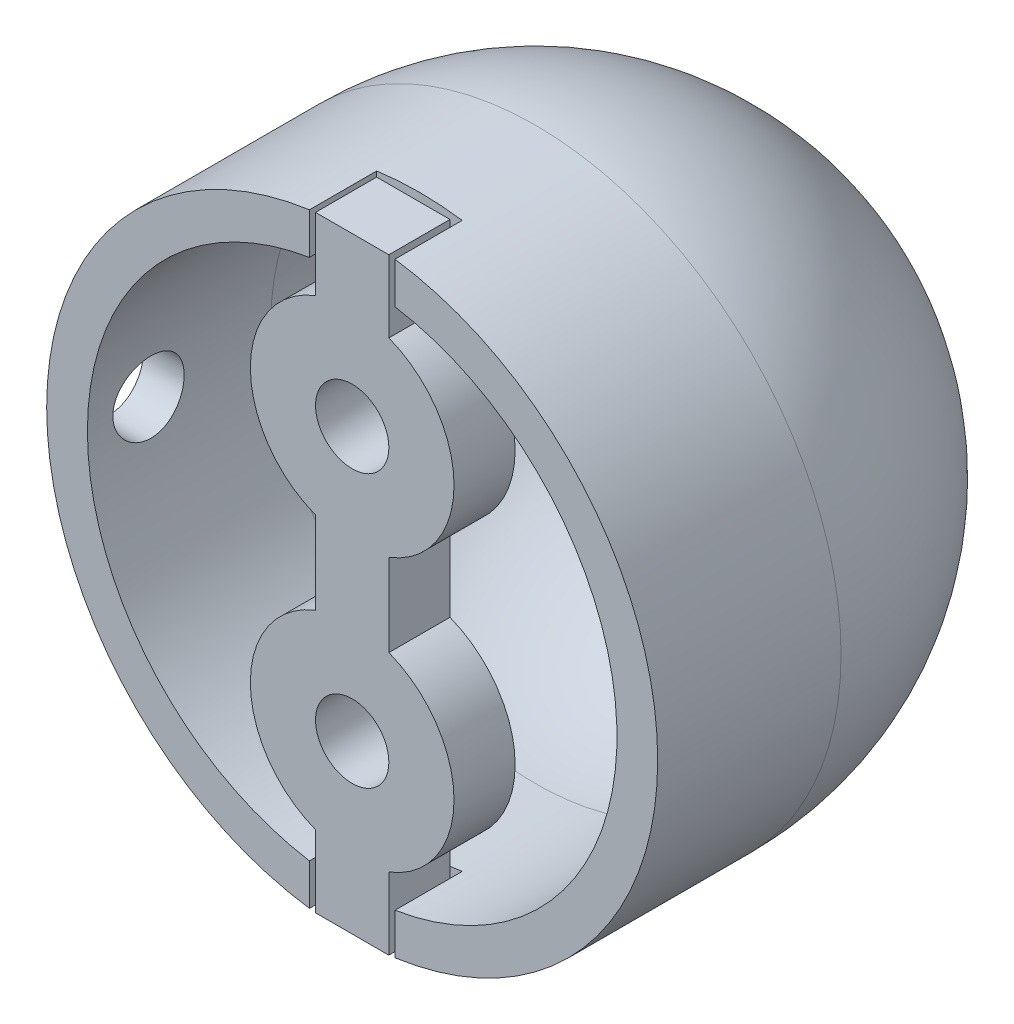
SolidWorks part; units mm, degrees
ref_plane "Front Plane" through (0, 0, 0) normal (0, 0, 1) x (1, 0, 0)
ref_plane "Top Plane" through (0, 0, 0) normal (0, 1, 0) x (1, 0, 0)
ref_plane "Right Plane" through (0, 0, 0) normal (1, 0, 0) x (0, 0, -1)
sketch "Sketch2" plane through (0, 0, 0) normal (0, 1, 0) x (1, 0, 0)
  line L19 (0, 0) -> (0, -9)
  line L20 (0, -9) -> (2, -9)
  line L30 (28, -8.3222) -> (28, -9)
  line L31 (28, -9) -> (30, -9)
  line L32 (2, -7) -> (28, -7) construction
  line L33 (0, -9) -> (30, -9) construction
  line L34 (2, 0) -> (2, -7) construction
  line L35 (28, 0) -> (28, -7) construction
  line L36 (2, 0) -> (2, -9)
  line L37 (28, 0) -> (28, -9)
  line L38 (15, 26.392) -> (15, -5.1789) construction
  line L39 (31.2383, -7.5) -> (-1.9776, -7.5) construction
  line L40 (30, 0) -> (30, -9) construction
  line L41 (30, 0) -> (30, -9)
  line L43 (15, 15) -> (15, 13)
  line L44 (0, -6) -> (2, -6)
  line L46 (34.9987, -7.7947) -> (34.8093, -7.7947)
  line L47 (34.9987, -7.7947) -> (34.9987, -6.81)
  line L48 (34.9987, -6.81) -> (34.8093, -6.81)
  line L49 (34.8093, -7.7947) -> (34.8093, -6.81)
  arc A2 (0, 0) -> (30, 0) centre (15, 0) cw
  arc A3 (2, 0) -> (28, 0) centre (15, 0) cw
  point P21 (15, 13)
  dimension "D1" = 2
  dimension "D2" = 22
  dimension "D3" = 3
  dimension "D4" = 1.5
  dimension "D5" = 26
revolve "Revolve3" add sketch "Sketch2" angle 360 about L38 region at (4.5759, 0, -10.4241) region at (1, 0, 7.5) other way angle 360
sketch "Sketch4" plane through (0, 0, 0) normal (1, 0, 0) x (0, 0, -1)
  line L0 (-9, 0) -> (-9, 13.7954) construction
  line L1 (-9, 0) -> (-4.2824, 0) construction
  line L2 (13.2, 0) -> (-13.2, 0) construction
  line L3 (-6, 0) -> (-6, 5.4849) construction
  line L4 (-9, 15) -> (-9, -15) construction
  circle A0 centre (-6, 0) radius 1.75
  dimension "D1" = 3
  dimension "D2" = 0
extrude "Cut-Extrude1" cut sketch "Sketch4" along normal blind 10 contours A0
ref_plane "Plane1" through (0, 0, 9) normal (0, 0, 1) x (1, 0, 0)
sketch "Sketch5" plane through (0, 0, 9) normal (0, 0, 1) x (1, 0, 0)
  line L0 (30, 0) -> (0, 0) construction
  line L1 (15, -13) -> (15, 15) construction
  line L2 (15, -4.8901) -> (30, 0) construction
  line L3 (30, 0) -> (15, 4.8901) construction
  line L4 (16.8, -6.6901) -> (16.8, 6.6901)
  line L5 (16.8, 6.6901) -> (16.8, 14.8916)
  line L6 (16.8, 14.8916) -> (13.2, 14.8916)
  line L7 (13.2, 14.8916) -> (13.2, 6.6901)
  line L8 (13.2, 6.6901) -> (13.2, -6.6901)
  line L9 (13.2, -6.6901) -> (13.2, -14.8916)
  line L10 (13.2, -14.8916) -> (16.8, -14.8916)
  line L11 (16.8, -14.8916) -> (16.8, -6.6901)
  line L13 (17.1, -15) -> (12.9, -15)
  line L14 (17.1, -15) -> (17.1, 15)
  line L15 (17.1, 15) -> (12.9, 15)
  line L16 (12.9, -15) -> (12.9, 15)
  circle A0 centre (15, 0) radius 13 construction
  circle A1 centre (15, 0) radius 15 construction
  circle A2 centre (15, 6.6901) radius 1.8
  circle A3 centre (15, -6.6901) radius 1.8
  circle A4 centre (15, -6.6901) radius 5
  circle A5 centre (15, 6.6901) radius 5
  dimension "D1" = 0.3
  dimension "D2" = 0.3
extrude "Boss-Extrude1" add sketch "Sketch5" against normal blind 3 separate body contours L11 A4 L4 | L9 A4 L11 A3 | L8 A4 L9 | L4 A4 L8 A3 | L7 A5 L8 | L5 A5 L7 A2 | L4 A5 L5 | L8 A5 L4 A2 | A5 L8 A4 L4 | L16 A5 | L14 A5 | L16 A4 | L14 A4 | A4 L9 L10 L11 | A5 L5 L6 L7 region at (15, -3.5601, 9) region at (16.9493, -6.6901, 9) region at (15, -9.82, 9) region at (15, 0, 9) region at (15, -13.2342, 9) region at (13.0507, -6.6901, 9) region at (15, 3.5601, 9) region at (16.9493, 6.6901, 9) region at (18.2947, -6.6901, 9) region at (15, 9.82, 9) region at (13.0507, 6.6901, 9) region at (18.2947, 6.6901, 9) region at (11.7053, -6.6901, 9) region at (15, 13.2342, 9) region at (11.7053, 6.6901, 9)
extrude "Cut-Extrude3" cut sketch "Sketch5<3>" against normal blind 20 contours A2 | A3 region at (15, -6.6901, 9) region at (15, 6.6901, 9)
sketch "Sketch5<3>" plane through (0, 0, 9) normal (0, 0, 1) x (1, 0, 0) same geometry as "Sketch5"
extrude "Cut-Extrude4" cut sketch "Sketch5<5>" against normal blind 3.3 contours A4 L16 L13 L14 L11 L10 L9 | A4 L9 L10 L11 | A5 L14 L15 L16 L7 L6 L5 | A5 L5 L6 L7 region at (16.9731, -11.3457, 9) region at (15, -13.2342, 9) region at (15, 13.2342, 9) region at (16.8565, 13.1232, 9)
sketch "Sketch5<5>" plane through (0, 0, 9) normal (0, 0, 1) x (1, 0, 0) same geometry as "Sketch5"
